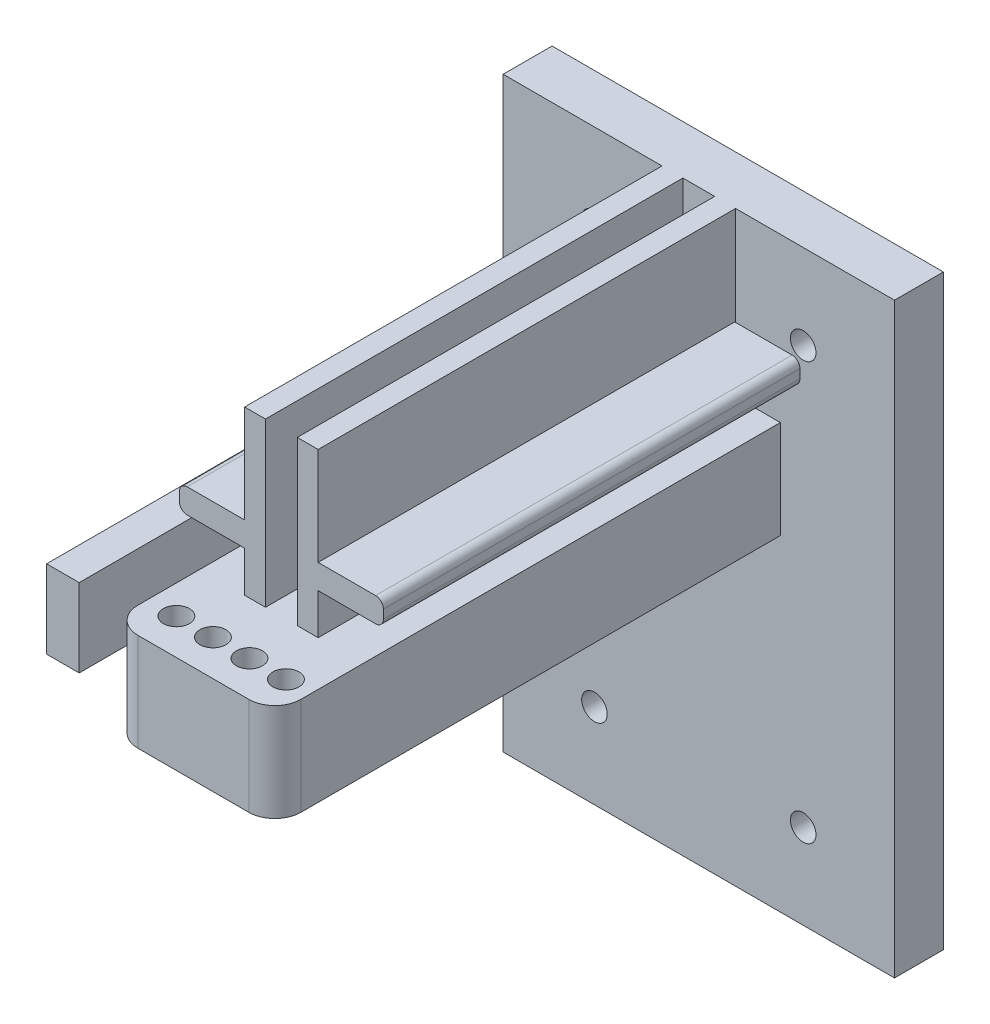
SolidWorks part; units mm, degrees
ref_plane "Front Plane" through (0, 0, 0) normal (0, 0, 1) x (1, 0, 0)
ref_plane "Top Plane" through (0, 0, 0) normal (0, 1, 0) x (1, 0, 0)
ref_plane "Right Plane" through (0, 0, 0) normal (1, 0, 0) x (0, 0, -1)
sketch "Sketch1" plane through (0, 0, 0) normal (0, 0, 1) x (1, 0, 0)
  line L1 (-19.05, -28.575) -> (19.05, -28.575)
  line L2 (-19.05, -28.575) -> (-19.05, 28.575)
  line L3 (-19.05, 28.575) -> (19.05, 28.575)
  line L4 (19.05, -28.575) -> (19.05, 28.575)
  line L5 (-19.05, -28.575) -> (19.05, 28.575) construction
  line L6 (-19.05, 28.575) -> (19.05, -28.575) construction
  point P0 (0, 0)
  dimension "D1" = 38.1
  dimension "D2" = 57.15
extrude "Boss-Extrude1" add sketch "Sketch1" along normal blind 4.7625
sketch "Sketch2" plane through (0, 0, 0) normal (0, 0, 1) x (1, 0, 0)
  line L0 (0, 0) -> (19.05, 0) construction
  line L7 (19.05, -28.575) -> (19.05, 28.575) construction
  line L9 (19.05, 28.575) -> (-19.05, 28.575) construction
  line L10 (0, 0) -> (0, 28.575) construction
  circle A4 centre (10.16, 20.32) radius 1.2446
  circle A5 centre (-10.16, 20.32) radius 1.2446
  circle A6 centre (10.16, -20.32) radius 1.2446
  circle A7 centre (-10.16, -20.32) radius 1.2446
  point P0 (0, 0)
  dimension "D1" = 10.16
  dimension "D2" = 2.4892
  dimension "D5" = 20.32
extrude "Cut-Extrude1" cut sketch "Sketch2" along normal blind 4.7625
sketch "Sketch4" plane through (0, 0, 4.7625) normal (0, 0, 1) x (1, 0, 0)
  line L0 (0, -28.575) -> (0, 28.575) construction
  line L1 (-19.05, -28.575) -> (19.05, -28.575) construction
  line L2 (19.05, 28.575) -> (-19.05, 28.575) construction
  line L3 (-19.05, 0) -> (19.05, 0) construction
  line L4 (-19.05, 28.575) -> (-19.05, -28.575) construction
  line L5 (19.05, -28.575) -> (19.05, 28.575) construction
  line L6 (-19.05, 3.175) -> (19.05, 3.175) construction
  line L7 (-7.9375, 3.175) -> (7.9375, 3.175)
  line L8 (-41.275, -41.275) -> (41.275, -41.275) construction
  line L9 (-41.275, -41.275) -> (-41.275, 41.275) construction
  line L10 (-41.275, 41.275) -> (41.275, 41.275) construction
  line L11 (41.275, -41.275) -> (41.275, 41.275) construction
  line L12 (-41.275, -41.275) -> (41.275, 41.275) construction
  line L13 (-41.275, 41.275) -> (41.275, -41.275) construction
  line L14 (-7.9375, 3.175) -> (-7.9375, 12.7)
  line L15 (7.9375, 3.175) -> (7.9375, 12.7)
  line L16 (-7.9375, 12.7) -> (7.9375, 12.7)
  point P14 (0, 0)
  point P23 (0, 12.7)
  dimension "D1" = 82.55
  dimension "D2" = 82.55
  dimension "D3" = 44.45
  dimension "D4" = 15.875
  dimension "D5" = 9.525
extrude "Boss-Extrude2" add sketch "Sketch4" along normal blind 49.2125
sketch "Sketch5" plane through (0, 12.7, 0) normal (0, 1, 0) x (1, 0, 0)
  line L0 (0, -4.7625) -> (0, -43.4412) construction
  line L1 (7.9375, -4.7625) -> (-7.9375, -4.7625) construction
  line L2 (7.9375, -53.975) -> (-7.9375, -53.975) construction
  line L3 (-7.9375, -42.8625) -> (-6.4135, -42.8625) construction
  line L4 (-7.9375, -53.975) -> (-7.9375, -4.7625) construction
  line L5 (7.9375, -53.975) -> (7.9375, -4.7625) construction
  line L6 (0, -42.8625) -> (0, -53.975) construction
  line L7 (0, -42.8625) -> (0, -53.975) construction
  line L8 (-3.8735, -42.8625) -> (7.9375, -42.8625) construction
  circle A4 centre (-5.1435, -50.4825) radius 1.27
  circle A14 centre (-1.5875, -50.4825) radius 1.27
  circle A16 centre (1.9685, -50.4825) radius 1.27
  circle A18 centre (5.5245, -50.4825) radius 1.27
  dimension "D2" = 5.1435
  dimension "D1" = 38.1
  dimension "D3" = 45.72
  dimension "D5" = 4
extrude "Cut-Extrude2" cut sketch "Sketch5" against normal up to next
fillet "Fillet2" radius 2.54 2 edges at (-7.9375, 7.9375, 53.975) (7.9375, 7.9375, 53.975)
ref_plane "Plane1" through (0, 0, 0) normal (-1, 0, 0) x (0, 0, 1)
sketch "Sketch8" plane through (0, 0, 4.7625) normal (0, 0, 1) x (1, 0, 0)
  line L0 (0, 28.575) -> (0, 12.7) construction
  line L1 (19.05, 28.575) -> (-19.05, 28.575) construction
  line L2 (7.9375, 12.7) -> (-7.9375, 12.7) construction
  line L3 (-4.572, 25.4) -> (4.572, 25.4) construction
  line L5 (-3.5801, 12.7) -> (-1.5481, 12.7)
  line L6 (-4.572, 25.4) -> (4.572, 25.4) construction
  line L7 (-4.572, 25.4) -> (-4.572, 12.7) construction
  line L8 (-4.572, 12.7) -> (4.572, 12.7) construction
  line L9 (4.572, 25.4) -> (4.572, 12.7) construction
  line L10 (-4.572, 25.4) -> (4.572, 12.7) construction
  line L11 (-4.572, 12.7) -> (4.572, 25.4) construction
  line L12 (-3.5801, 12.7) -> (-3.5801, 28.575)
  line L13 (-1.5481, 12.7) -> (-1.5481, 28.575)
  line L14 (-3.5801, 28.575) -> (-1.5481, 28.575)
  line L15 (3.5801, 12.7) -> (1.5481, 12.7)
  line L16 (3.5801, 12.7) -> (3.5801, 28.575)
  line L17 (3.5801, 28.575) -> (1.5481, 28.575)
  line L18 (1.5481, 12.7) -> (1.5481, 28.575)
  point P9 (0, 25.4)
  point P13 (0, 19.05)
  dimension "D1" = 9.144
  dimension "D3" = 1.9837
  dimension "D4" = 2.032
extrude "Boss-Extrude4" add sketch "Sketch8" along normal blind 40.64
sketch "Sketch9" plane through (-3.5801, 0, 0) normal (-1, 0, 0) x (0, 0, 1)
  line L0 (45.4025, 16.6687) -> (4.8502, 16.6687) construction
  line L1 (45.4025, 28.575) -> (45.4025, 12.7) construction
  line L2 (45.4025, 12.7) -> (4.7625, 12.7) construction
  line L3 (4.8502, 16.6687) -> (45.4025, 16.6687)
  line L4 (4.8502, 16.6687) -> (4.8502, 19.05)
  line L5 (45.4025, 16.6687) -> (45.4025, 19.05)
  line L6 (4.8502, 19.05) -> (45.4025, 19.05)
  dimension "D1" = 3.9688
  dimension "D2" = 2.3813
extrude "Boss-Extrude5" add sketch "Sketch9" along normal blind 6.35
fillet "Fillet4" radius 0.762 2 edges at (-9.9301, 16.6687, 25.1264) (-9.9301, 19.05, 25.1264)
mirror "Mirror2" about plane through (0, 0, 0) normal (-1, 0, 0) of "Boss-Extrude5", "Fillet4"
sketch "Sketch10" plane through (0, 0, 0) normal (0, 0, 1) x (1, 0, 0)
  line L0 (-34.925, -17.145) -> (-38.1, -17.145)
  line L1 (-41.275, -41.275) -> (41.275, -41.275) construction
  line L2 (-41.275, -41.275) -> (-41.275, 41.275) construction
  line L3 (-41.275, 41.275) -> (41.275, 41.275) construction
  line L4 (41.275, -41.275) -> (41.275, 41.275) construction
  line L5 (-41.275, -41.275) -> (41.275, 41.275) construction
  line L6 (-41.275, 41.275) -> (41.275, -41.275) construction
  line L7 (-19.05, -28.575) -> (-19.05, -9.525)
  line L8 (-19.05, 28.575) -> (-19.05, -28.575) construction
  line L9 (-19.05, -9.525) -> (-38.1, -9.525)
  line L10 (-38.1, -9.525) -> (-34.925, -9.525)
  line L11 (-38.1, -9.525) -> (-38.1, -17.145)
  line L15 (-34.925, -9.525) -> (-19.05, -9.525)
  line L17 (-34.925, -17.145) -> (-19.05, -17.145)
  line L18 (-19.05, -9.525) -> (-19.05, -17.145)
  line L19 (-34.925, -9.525) -> (-19.05, -17.145) construction
  line L20 (-34.925, -17.145) -> (-19.05, -9.525) construction
  point P0 (0, 0)
  point P17 (-26.9875, -13.335)
  dimension "D1" = 82.55
  dimension "D2" = 82.55
  dimension "D3" = 19.05
  dimension "D4" = 19.05
  dimension "D5" = 7.62
extrude "Boss-Extrude6" add sketch "Sketch10" along normal up to surface (4.7625 mm away) contours L0 L17 L7 L9 L11 region at (-28.575, -13.335, 0) up to face at (-8.9154, 20.32, 4.7625)
sketch "Sketch11" plane through (0, 0, 4.7625) normal (0, 0, 1) x (1, 0, 0)
  line L0 (-38.1, -17.145) -> (-19.05, -17.145) construction
  line L1 (-38.1, -9.525) -> (-34.925, -9.525)
  line L2 (-38.1, -9.525) -> (-38.1, -17.145)
  line L3 (-38.1, -17.145) -> (-34.925, -17.145)
  line L4 (-34.925, -9.525) -> (-34.925, -17.145)
  line L5 (-38.1, -9.525) -> (-34.925, -17.145) construction
  line L6 (-38.1, -17.145) -> (-34.925, -9.525) construction
  point P4 (-36.5125, -13.335)
  dimension "D1" = 3.175
extrude "Boss-Extrude7" add sketch "Sketch11" along normal blind 25.4
